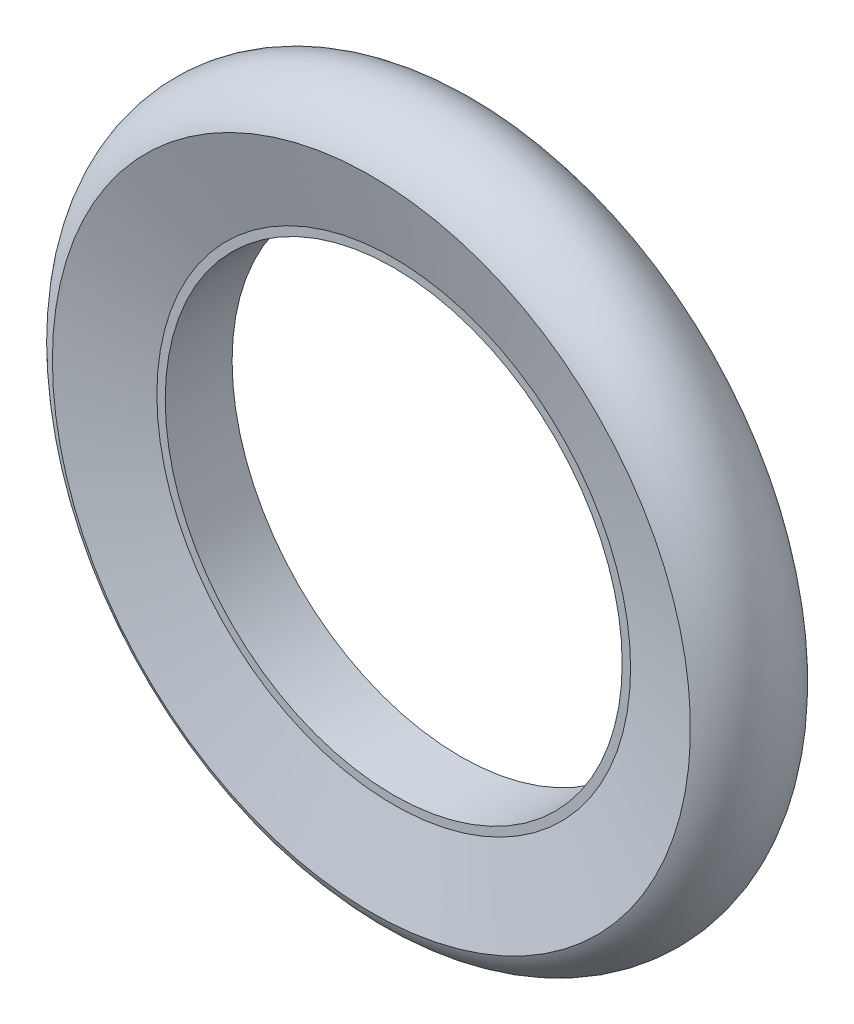
SolidWorks part; units mm, degrees
ref_plane "Спереди" through (0, 0, 0) normal (0, 0, 1) x (1, 0, 0)
ref_plane "Сверху" through (0, 0, 0) normal (0, 1, 0) x (1, 0, 0)
ref_plane "Справа" through (0, 0, 0) normal (1, 0, 0) x (0, 0, -1)
other "Configuration Table"
sketch "Sketch1" plane through (0, 0, 0) normal (0, 1, 0) x (1, 0, 0)
  line L1 (-291.9341, 0) -> (14.6359, 0) construction
  line L2 (0, 36.4643) -> (0, -49.4873) construction
  line L3 (-170, -24) -> (-229, -40)
  line L4 (-170, 24) -> (-229, 40)
  line L5 (-229, -40) -> (-229, 40) construction
  line L6 (-170, -24) -> (-164, -24)
  line L7 (-164, -24) -> (-164, 24)
  line L8 (-164, 24) -> (-170, 24)
  line L9 (-170, -24) -> (-170, 24) construction
  arc A1 (-229, -40) -> (-229, 40) centre (-211.2308, 0) cw
  dimension "D2" = 48
  dimension "D4" = 85
  dimension "D7" = 510
  dimension "D8" = 43.7692
  dimension "D1" = 6
  dimension "D3" = 164
  dimension "D5" = 26
  dimension "D6" = 80
revolve "Revolve1" add sketch "Sketch1" angle 360 about L2 region at (-210.3166, 0, 0)
equation "\"65.00mmф\"=65"
